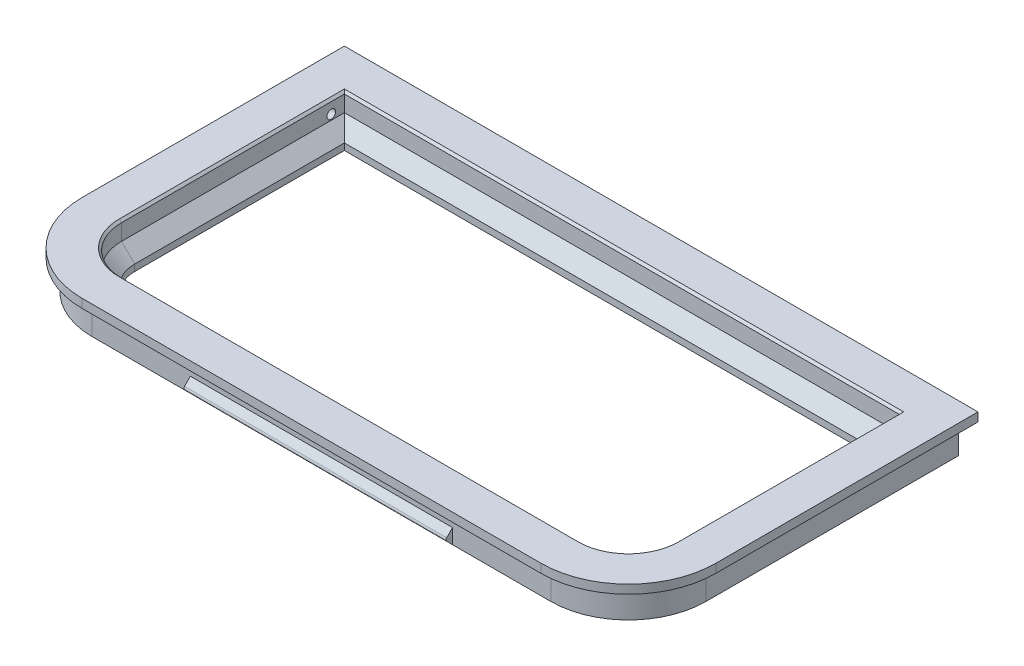
SolidWorks part; units mm, degrees
material "ПК/АБС"
ref_plane "Спереди" through (0, 0, 0) normal (0, 0, 1) x (1, 0, 0)
ref_plane "Сверху" through (0, 0, 0) normal (0, 1, 0) x (1, 0, 0)
ref_plane "Справа" through (0, 0, 0) normal (1, 0, 0) x (0, 0, -1)
sketch "Эскиз1" plane through (0, 0, 0) normal (0, 1, 0) x (1, 0, 0)
  line L1 (-72.5, -40) -> (72.5, -40)
  line L2 (-72.5, -40) -> (-72.5, 40)
  line L3 (-72.5, 40) -> (72.5, 40)
  line L4 (72.5, -40) -> (72.5, 40)
  line L5 (-72.5, -40) -> (72.5, 40) construction
  line L6 (-72.5, 40) -> (72.5, -40) construction
  point P0 (0, 0)
  dimension "D1" = 145
  dimension "D2" = 80
extrude "Бобышка-Вытянуть1" add sketch "Эскиз1" along normal blind 2
fillet "Скругление1" radius 20 2 edges at (-72.5, 1, 40) (72.5, 1, 40)
sketch "Эскиз2" plane through (0, 2, 0) normal (0, 1, 0) x (1, 0, 0)
  line L8 (-63.5, 31) -> (-63.5, -20)
  line L9 (-52.5, -31) -> (52.5, -31)
  line L10 (63.5, -20) -> (63.5, 31)
  line L11 (63.5, 31) -> (-63.5, 31)
  line L12 (-63.5, 31) -> (-63.5, -20)
  line L13 (-52.5, -31) -> (52.5, -31)
  line L14 (63.5, -20) -> (63.5, 31)
  line L15 (63.5, 31) -> (-63.5, 31)
  arc A4 (-63.5, -20) -> (-52.5, -31) centre (-52.5, -20) ccw
  arc A5 (52.5, -31) -> (63.5, -20) centre (52.5, -20) ccw
  arc A6 (-63.5, -20) -> (-52.5, -31) centre (-52.5, -20) ccw
  arc A7 (52.5, -31) -> (63.5, -20) centre (52.5, -20) ccw
  dimension "D1" = 9
extrude "Вырез-Вытянуть1" cut sketch "Эскиз2" against normal blind 2
sketch "Эскиз3" plane through (0, 0, 0) normal (0, -1, 0) x (1, 0, 0)
  line L15 (-63.5, -31) -> (-63.5, 20) construction
  line L16 (63.5, -31) -> (-63.5, -31) construction
  line L17 (63.5, 20) -> (63.5, -31) construction
  line L18 (-52.5, 31) -> (52.5, 31) construction
  line L19 (70.25, -37.75) -> (70.25, 20)
  line L20 (-70.25, -37.75) -> (70.25, -37.75)
  line L21 (-70.25, 20) -> (-70.25, -37.75)
  line L22 (52.5, 37.75) -> (-52.5, 37.75)
  line L23 (70.25, -37.75) -> (70.25, 20)
  line L24 (-70.25, -37.75) -> (70.25, -37.75)
  line L25 (-70.25, 20) -> (-70.25, -37.75)
  line L26 (52.5, 37.75) -> (-52.5, 37.75)
  line L27 (-63.5, -31) -> (-63.5, 20)
  line L28 (63.5, -31) -> (-63.5, -31)
  line L29 (63.5, 20) -> (63.5, -31)
  line L30 (-52.5, 31) -> (52.5, 31)
  arc A6 (-52.5, 31) -> (-63.5, 20) centre (-52.5, 20) ccw construction
  arc A7 (63.5, 20) -> (52.5, 31) centre (52.5, 20) ccw construction
  arc A8 (70.25, 20) -> (52.5, 37.75) centre (52.5, 20) ccw
  arc A9 (-52.5, 37.75) -> (-70.25, 20) centre (-52.5, 20) ccw
  arc A10 (70.25, 20) -> (52.5, 37.75) centre (52.5, 20) ccw
  arc A11 (-52.5, 37.75) -> (-70.25, 20) centre (-52.5, 20) ccw
  arc A12 (-52.5, 31) -> (-63.5, 20) centre (-52.5, 20) ccw
  arc A13 (63.5, 20) -> (52.5, 31) centre (52.5, 20) ccw
  dimension "D1" = 6.75
extrude "Бобышка-Вытянуть2" add sketch "Эскиз3" along normal blind 2
sketch "Эскиз5" plane through (0, 0, 0) normal (1, 0, 0) x (0, 0, -1)
  line L0 (-20, 0) -> (40, 0) construction
  line L7 (37.75, -2) -> (31, -2)
  line L9 (31, -2) -> (31, -6.7)
  line L10 (31, -6.7) -> (37.75, -6.7)
  line L11 (37.75, -6.7) -> (39.45, -5)
  line L12 (39.45, -5) -> (37.75, -3.3)
  line L13 (37.75, -3.3) -> (37.75, -2)
  line L14 (31, -2) -> (31, 2) construction
  line L15 (31, -2) -> (31, 2) construction
  line L16 (-31, -2) -> (-31, 2) construction
  line L17 (-31, -2) -> (-31, 2) construction
  line L18 (-31, -2) -> (-31, -6.7)
  line L19 (-31, -6.7) -> (-37.75, -6.7)
  line L20 (-37.75, -6.7) -> (-39.45, -5)
  line L21 (-39.45, -5) -> (-37.75, -3.3)
  line L22 (-37.75, -3.3) -> (-37.75, -2)
  line L23 (-37.75, -2) -> (-31, -2)
  dimension "D1" = 5
  dimension "D2" = 1.7
  dimension "D4" = 1.7
extrude "Бобышка-Вытянуть4" add sketch "Эскиз5" along normal mid plane 15
sketch "Эскиз6" plane through (0, 0, 0) normal (1, 0, 0) x (0, 0, -1)
  line L6 (-39.45, -5) -> (-37.75, -6.7)
  line L7 (-37.75, -6.7) -> (-31, -6.7)
  line L8 (-31, -6.7) -> (-31, -2)
  line L9 (-31, -2) -> (-37.75, -2)
  line L10 (-37.75, -2) -> (-37.75, -3.3)
  line L11 (-37.75, -3.3) -> (-39.45, -5)
  line L12 (-39.45, -5) -> (-37.75, -6.7)
  line L13 (-37.75, -6.7) -> (-31, -6.7)
  line L14 (-31, -6.7) -> (-31, -2)
  line L15 (-31, -2) -> (-37.75, -2)
  line L16 (-37.75, -2) -> (-37.75, -3.3)
  line L17 (-37.75, -3.3) -> (-39.45, -5)
  dimension "D1" = 0
extrude "Бобышка-Вытянуть5" add sketch "Эскиз6" along normal mid plane 60
fillet "Скругление2" radius 0.5 2 edges at (0, -5, 39.45) (0, -5, -39.45)
sketch "Эскиз7" plane through (0, -2, 0) normal (0, -1, 0) x (1, 0, 0)
  line L8 (-52.5, 31) -> (-30, 31)
  line L9 (-30, 31) -> (-30, 37.75)
  line L10 (-30, 37.75) -> (-52.5, 37.75)
  line L11 (-70.25, 20) -> (-70.25, -37.75)
  line L12 (-70.25, -37.75) -> (-7.5, -37.75)
  line L13 (-7.5, -37.75) -> (-7.5, -31)
  line L14 (-7.5, -31) -> (-63.5, -31)
  line L15 (-63.5, -31) -> (-63.5, 20)
  line L16 (-52.5, 31) -> (-30, 31)
  line L17 (-30, 31) -> (-30, 37.75)
  line L18 (-30, 37.75) -> (-52.5, 37.75)
  line L19 (-70.25, 20) -> (-70.25, -37.75)
  line L20 (-70.25, -37.75) -> (-7.5, -37.75)
  line L21 (-7.5, -37.75) -> (-7.5, -31)
  line L22 (-7.5, -31) -> (-63.5, -31)
  line L23 (-63.5, -31) -> (-63.5, 20)
  line L24 (30, 37.75) -> (30, 31)
  line L25 (30, 31) -> (52.5, 31)
  line L26 (63.5, 20) -> (63.5, -31)
  line L27 (63.5, -31) -> (7.5, -31)
  line L28 (7.5, -31) -> (7.5, -37.75)
  line L29 (7.5, -37.75) -> (70.25, -37.75)
  line L30 (70.25, -37.75) -> (70.25, 20)
  line L31 (52.5, 37.75) -> (30, 37.75)
  line L32 (30, 37.75) -> (30, 31)
  line L33 (30, 31) -> (52.5, 31)
  line L34 (63.5, 20) -> (63.5, -31)
  line L35 (63.5, -31) -> (7.5, -31)
  line L36 (7.5, -31) -> (7.5, -37.75)
  line L37 (7.5, -37.75) -> (70.25, -37.75)
  line L38 (70.25, -37.75) -> (70.25, 20)
  line L39 (52.5, 37.75) -> (30, 37.75)
  arc A2 (-52.5, 37.75) -> (-70.25, 20) centre (-52.5, 20) ccw
  arc A3 (-52.5, 31) -> (-63.5, 20) centre (-52.5, 20) ccw
  arc A4 (-52.5, 37.75) -> (-70.25, 20) centre (-52.5, 20) ccw
  arc A5 (-52.5, 31) -> (-63.5, 20) centre (-52.5, 20) ccw
  arc A6 (63.5, 20) -> (52.5, 31) centre (52.5, 20) ccw
  arc A7 (70.25, 20) -> (52.5, 37.75) centre (52.5, 20) ccw
  arc A8 (63.5, 20) -> (52.5, 31) centre (52.5, 20) ccw
  arc A9 (70.25, 20) -> (52.5, 37.75) centre (52.5, 20) ccw
  dimension "D1" = 0
  dimension "D2" = 0
extrude "Бобышка-Вытянуть6" add sketch "Эскиз7" along normal up to surface (4.7 mm away) up to face at (0, -6.7, 34.375)
sketch "Эскиз10" plane through (0, -6.7, 0) normal (0, -1, 0) x (1, 0, 0)
  line L14 (-63.5, 20) -> (-63.5, -31) construction
  line L15 (63.5, -31) -> (-63.5, -31) construction
  line L16 (63.5, -31) -> (63.5, 20) construction
  line L17 (52.5, 31) -> (-52.5, 31) construction
  line L18 (60.5, -28) -> (60.5, 20)
  line L19 (-60.5, -28) -> (60.5, -28)
  line L20 (-60.5, 20) -> (-60.5, -28)
  line L21 (52.5, 28) -> (-52.5, 28)
  line L22 (60.5, -28) -> (60.5, 20)
  line L23 (-60.5, -28) -> (60.5, -28)
  line L24 (-60.5, 20) -> (-60.5, -28)
  line L25 (52.5, 28) -> (-52.5, 28)
  line L26 (-63.5, 20) -> (-63.5, -31)
  line L27 (63.5, -31) -> (-63.5, -31)
  line L28 (63.5, -31) -> (63.5, 20)
  line L29 (52.5, 31) -> (-52.5, 31)
  arc A7 (-52.5, 31) -> (-63.5, 20) centre (-52.5, 20) ccw construction
  arc A8 (63.5, 20) -> (52.5, 31) centre (52.5, 20) ccw construction
  arc A9 (60.5, 20) -> (52.5, 28) centre (52.5, 20) ccw
  arc A10 (-52.5, 28) -> (-60.5, 20) centre (-52.5, 20) ccw
  arc A11 (60.5, 20) -> (52.5, 28) centre (52.5, 20) ccw
  arc A12 (-52.5, 28) -> (-60.5, 20) centre (-52.5, 20) ccw
  arc A13 (-52.5, 31) -> (-63.5, 20) centre (-52.5, 20) ccw
  arc A14 (63.5, 20) -> (52.5, 31) centre (52.5, 20) ccw
  dimension "D1" = 3
extrude "Бобышка-Вытянуть9" add sketch "Эскиз10" against normal blind 1.5
chamfer "Фаска2" distance 3 angle 45 6 edges at (0, -5.2, -31) (63.5, -5.2, -5.5) (-63.5, -5.2, -5.5) (60.2782, -5.2, 27.7782) (-60.2782, -5.2, 27.7782) (0, -5.2, 31)
sketch "Эскиз11" plane through (70.25, 0, 0) normal (1, 0, 0) x (0, 0, -1)
  line L0 (40, 2) -> (40, 0) construction
  line L1 (-20, 2) -> (40, 2) construction
  circle A0 centre (28, -1) radius 1
  dimension "D1" = 2
  dimension "D2" = 12
  dimension "D3" = 3
extrude "Вырез-Вытянуть2" cut sketch "Эскиз11" against normal through all
chamfer "Фаска3" distance 0.5 angle 45 6 edges at (63.5, 2, -5.5) (60.2782, 2, 27.7782) (0, 2, 31) (-60.2782, 2, 27.7782) (-63.5, 2, -5.5) (0, 2, -31)
